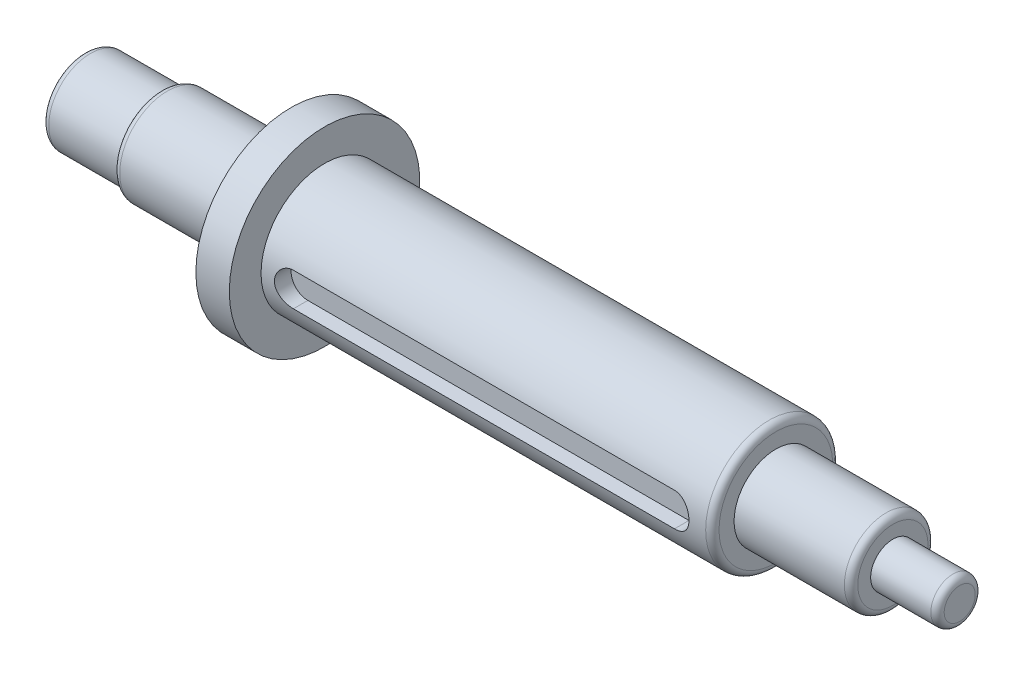
SolidWorks part; units mm, degrees
ref_plane "Спереди" through (0, 0, 0) normal (0, 0, 1) x (1, 0, 0)
ref_plane "Сверху" through (0, 0, 0) normal (0, 1, 0) x (1, 0, 0)
ref_plane "Справа" through (0, 0, 0) normal (1, 0, 0) x (0, 0, -1)
sketch "Эскиз1" plane through (0, 0, 0) normal (0, 1, 0) x (1, 0, 0)
  line L0 (0, 0) -> (262, 0) construction
  line L1 (0, 0) -> (0, 12.5)
  line L2 (0, 12.5) -> (23, 12.5)
  line L3 (23, 12.5) -> (23, 14.25)
  line L4 (23, 14.25) -> (62, 14.25)
  line L5 (62, 14.25) -> (62, 28.5)
  line L6 (62, 28.5) -> (72, 28.5)
  line L7 (72, 28.5) -> (72, 19)
  line L8 (72, 19) -> (207, 19)
  line L9 (207, 19) -> (207, 12.5)
  line L10 (207, 12.5) -> (242, 12.5)
  line L11 (242, 12.5) -> (242, 6.65)
  line L12 (242, 6.65) -> (262, 6.65)
  line L13 (262, 6.65) -> (262, 0)
  line L14 (0, 0) -> (262, 0)
  dimension "D1" = 25
  dimension "D2" = 28.5
  dimension "D3" = 57
  dimension "D4" = 38
  dimension "D5" = 25
  dimension "D6" = 13.3
  dimension "D7" = 23
  dimension "D8" = 62
  dimension "D9" = 262
  dimension "D10" = 20
  dimension "D11" = 55
  dimension "D12" = 190
revolve "Повернуть1" add sketch "Эскиз1" angle 360 about L0
fillet "Скругление1" radius 2 5 edges at (262, 0, 6.65) (242, 0, 12.5) (207, 0, 19) (23, 0, 14.25) (0, 0, 12.5)
ref_plane "Плоскость4" through (0, 0, 19) normal (0, 0, 1) x (1, 0, 0)
sketch "Эскиз2" plane through (0, 0, 19) normal (0, 0, 1) x (1, 0, 0)
  line L0 (81, 0) -> (195, 0) construction
  line L3 (81, 5) -> (195, 5)
  line L4 (81, -5) -> (195, -5)
  line L5 (72, -28.5) -> (72, 28.5) construction
  line L6 (205, 19) -> (205, -19) construction
  arc A2 (81, 5) -> (81, -5) centre (81, 0) ccw
  arc A3 (195, -5) -> (195, 5) centre (195, 0) ccw
  point P2 (138, 0)
  dimension "D3" = 5
  dimension "D1" = 9
  dimension "D2" = 10
extrude "Вырез-Вытянуть1" cut sketch "Эскиз2" against normal blind 5
